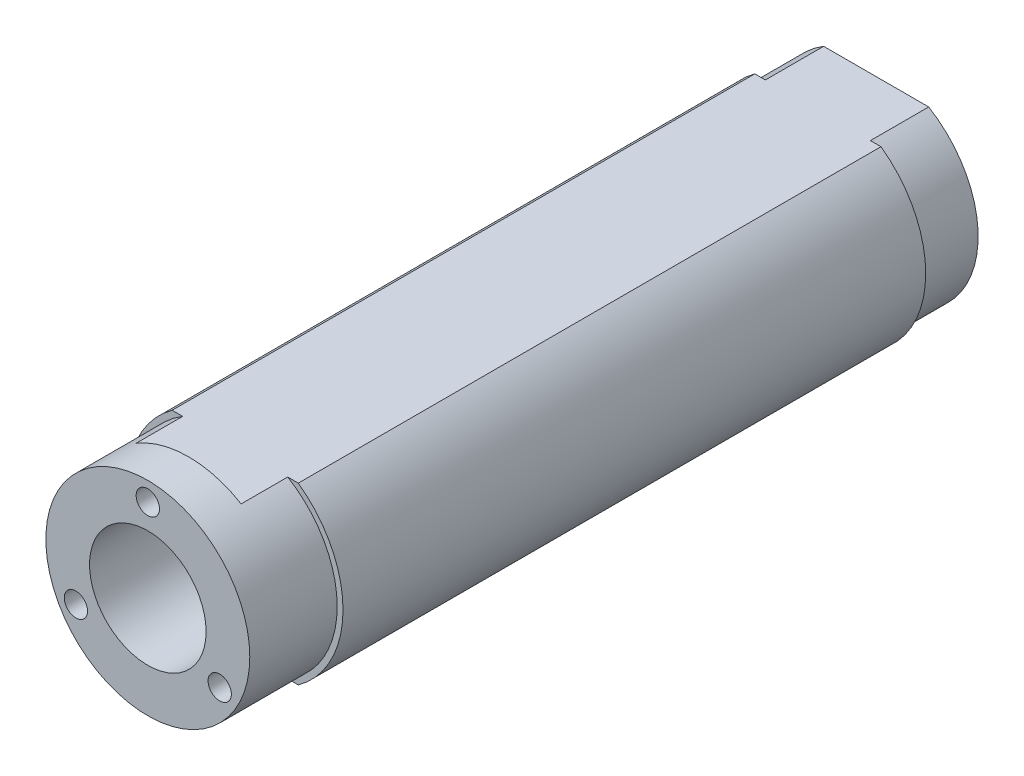
SolidWorks part; units mm, degrees
ref_plane "Front Plane" through (0, 0, 0) normal (0, 0, 1) x (1, 0, 0)
ref_plane "Top Plane" through (0, 0, 0) normal (0, 1, 0) x (1, 0, 0)
ref_plane "Right Plane" through (0, 0, 0) normal (1, 0, 0) x (0, 0, -1)
sketch "Sketch1" plane through (0, 0, 0) normal (0, 0, 1) x (1, 0, 0)
  line L0 (0, 24.7328) -> (0, -23.7417) construction
  line L1 (-10.8282, 15) -> (10.8282, 15)
  line L2 (-10.8282, -15) -> (10.8282, -15)
  circle A0 centre (0, 0) radius 10
  circle A1 centre (0, 0) radius 17.5
  circle A2 centre (0, 0) radius 18.5
  point P6 (0, 15)
  point P7 (0, -15)
  dimension "D1" = 15
  dimension "D2" = 37
  dimension "D3" = 35
  dimension "D5" = 15
  dimension "D4" = 20
extrude "Boss-Extrude1" add sketch "Sketch1" along normal blind 65 and the other way blind 60 contours L1 L0 A0 L2 A1 | L0 L1 A1 L2 A0 region at (4.5069, 14.6527, 0) region at (-0.3473, 12.5, 0)
extrude "Boss-Extrude2" add sketch "Sketch1<23>" along normal blind 50 and the other way blind 50 contours L2 A2 L1 A1 | L1 A2 L2 A1 region at (-9.921, 14.6854, 0) region at (16.1906, 8.2807, 0)
sketch "Sketch1<23>" plane through (0, 0, 0) normal (0, 0, 1) x (1, 0, 0) same geometry as "Sketch1"
ref_plane "Plane1" through (0, 0, 65) normal (0, 0, 1) x (1, 0, 0)
sketch "Sketch5" plane through (0, 0, 65) normal (0, 0, 1) x (1, 0, 0)
  line L0 (0, 24.7328) -> (0, -23.7417) construction
  line L1 (-10.8282, 15) -> (10.8282, 15)
  line L2 (-10.8282, -15) -> (10.8282, -15)
  circle A0 centre (0, 0) radius 10
  circle A1 centre (0, 0) radius 17.5
  circle A2 centre (0, 0) radius 18.5
  point P6 (0, 15)
  point P7 (0, -15)
  dimension "D1" = 15
  dimension "D2" = 37
  dimension "D3" = 35
  dimension "D5" = 15
  dimension "D4" = 20
extrude "Boss-Extrude3" add sketch "Sketch5" against normal blind 7 contours L0 L1 A1 L2 A0 | L1 L0 A0 L2 A1 | L0 A1 L1 | A1 L0 L1 | L2 L0 A1 | L0 L2 A1 region at (3.4149, 16.0064, 65) region at (-3.4149, 16.0064, 65) region at (4.5069, 14.6527, 65) region at (-0.3473, 12.5, 65) region at (-3.4149, -16.0064, 65) region at (3.4149, -16.0064, 65)
sketch "Sketch6" plane through (0, 0, 65) normal (0, 0, 1) x (1, 0, 0)
  line L0 (0, 0) -> (0, 22.9778) construction
  circle A0 centre (0, 14.25) radius 2
  circle A1 centre (12.3409, -7.125) radius 2
  circle A2 centre (-12.3409, -7.125) radius 2
  point P3 (0, 14.25)
  point P13 (0, 0)
  dimension "D2" = 4
  dimension "D1" = 14.25
  dimension "D3" = 3
extrude "Cut-Extrude1" cut sketch "Sketch6" against normal blind 5
ref_plane "Plane2" through (0, 0, -57) normal (0, 0, -1) x (-1, 0, 0)
hole_wizard "M3 Tapped Hole1" positions "Sketch8" profile "Sketch9" tap size "M3" standard "ISO"
sketch "Sketch8" plane through (0, -15, 0) normal (0, -1, 0) x (-1, 0, 0)
  point P0 (0, 0)
sketch "Sketch9" plane through (0, -15, 0) normal (1, 0, 0) x (0, 0, -1)
  line L0 (0, 0) -> (0, 8.2511)
  line L1 (0, 8.2511) -> (1.25, 7.5)
  line L2 (1.25, 7.5) -> (1.25, 0.275)
  line L3 (1.25, 0.275) -> (1.525, 0)
  line L5 (1.525, 0) -> (0, 0)
  line L6 (-1.25, 0.275) -> (-1.525, 0) construction
  line L10 (0, 8.2511) -> (-1.25, 7.5) construction
  line L11 (0, -6.35) -> (0, 107.95) construction
  dimension "Tap Drill Dia." = 2.5
  dimension "Tap Drill Depth" = 7.5
  dimension "Near C'Sink Dia." = 3.05
  dimension "Near C'Sink Angle" = 90
  dimension "Drill Angle" = 118
